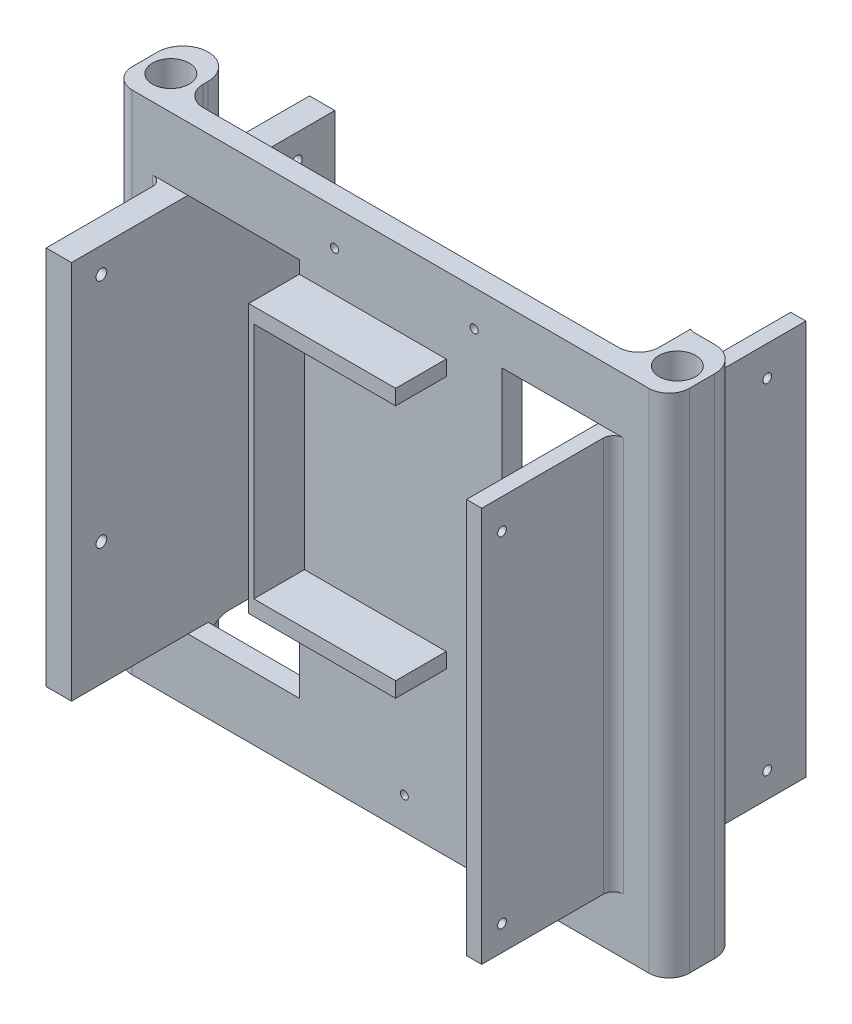
SolidWorks part; units mm, degrees
ref_plane "Front Plane" through (0, 0, 0) normal (0, 0, 1) x (1, 0, 0)
ref_plane "Top Plane" through (0, 0, 0) normal (0, 1, 0) x (1, 0, 0)
ref_plane "Right Plane" through (0, 0, 0) normal (1, 0, 0) x (0, 0, -1)
sketch "Sketch2" plane through (0, 0, 0) normal (0, 1, 0) x (1, 0, 0)
  line L0 (0, 11.43) -> (0, 5.08)
  line L1 (5.08, 0) -> (134.62, 0)
  line L2 (139.7, 5.08) -> (139.7, 11.43)
  line L3 (12.7, 11.43) -> (12.7, 5.08)
  line L4 (12.7, 5.08) -> (127, 5.08)
  line L5 (127, 5.08) -> (127, 11.43)
  line L6 (6.35, 0) -> (6.35, 3.81) construction
  line L7 (127, 11.43) -> (127, 17.78)
  line L8 (127, 17.78) -> (133.35, 17.78)
  arc A2 (12.7, 11.43) -> (0, 11.43) centre (6.35, 11.43) ccw
  arc A3 (139.7, 11.43) -> (133.35, 17.78) centre (133.35, 11.43) ccw
  circle A4 centre (6.35, 8.4138) radius 4.6037
  circle A5 centre (133.35, 8.4138) radius 4.6037
  arc A6 (134.62, 0) -> (139.7, 5.08) centre (134.62, 5.08) ccw
  arc A7 (0, 5.08) -> (5.08, 0) centre (5.08, 5.08) ccw
  point P12 (38.0611, -3.1951)
  point P23 (0, 0)
  dimension "D1" = 9.2075
  dimension "D5" = 5.08
  dimension "D2" = 127
  dimension "D3" = 139.7
  dimension "D4" = 5.08
  dimension "D6" = 3.81
extrude "Boss-Extrude1" add sketch "Sketch2" along normal blind 127 contours L5 L7 L8 A3 L2 A6 L1 A7 L0 A2 L3 L4
sketch "Sketch3" plane through (0, 127, 0) normal (0, 1, 0) x (1, 0, 0)
  circle A0 centre (133.35, 8.4138) radius 4.6037 construction
  circle A1 centre (6.35, 8.4138) radius 4.6037 construction
  circle A2 centre (133.35, 8.4138) radius 4.6037
  circle A3 centre (6.35, 8.4138) radius 4.6037
extrude "Cut-Extrude1" cut sketch "Sketch3" against normal up to surface (127 mm away) up to face at (75.7423, 0, -8.7028)
sketch "Sketch4" plane through (0, 0, 0) normal (0, 0, 1) x (1, 0, 0)
  line L0 (44.936, 120.65) -> (44.936, 11.4099) construction
  line L2 (-49.3824, 53.26) -> (90.3176, 53.26) construction
  line L8 (5.08, 127) -> (134.62, 127) construction
  line L9 (127, 127) -> (127, 0) construction
  line L10 (127, 127) -> (127, 0) construction
  line L11 (12.7, 127) -> (12.7, 0) construction
  line L12 (12.7, 127) -> (12.7, 0) construction
  circle A0 centre (69.32, 86.76) radius 1.35
  circle A1 centre (20.32, 86.76) radius 1.35
  circle A2 centre (20.32, 28.76) radius 1.35
  circle A3 centre (69.32, 28.76) radius 1.35
  circle A4 centre (62.436, 10.65) radius 1
  circle A5 centre (62.436, 95.65) radius 1
  circle A6 centre (44.936, 120.65) radius 1
  circle A7 centre (27.436, 95.65) radius 1
  circle A8 centre (27.436, 10.65) radius 1
  point P25 (83.5986, 53.26)
  point P30 (-32.3911, 53.26)
  dimension "D5" = 2.7
  dimension "D6" = 2
  dimension "D1" = 49
  dimension "D2" = 58
  dimension "D3" = 24.5
  dimension "D4" = 24.384
  dimension "D7" = 35
  dimension "D8" = 17.5
  dimension "D9" = 25
  dimension "D10" = 85
  dimension "D11" = 8.89
  dimension "D12" = 6.35
  dimension "D13" = 7.62
extrude "Cut-Extrude2" [suppressed] cut sketch "Sketch4" against normal up to surface (5.08 mm away)
sketch "Sketch12" plane through (0, 0, 0) normal (0, -1, 0) x (1, 0, 0)
  line L5 (127, -5.08) -> (68.58, -5.08)
  line L6 (127, -5.08) -> (127, -43.18)
  line L7 (127, -43.18) -> (68.58, -43.18)
  line L8 (68.58, -5.08) -> (68.58, -43.18)
  dimension "D1" = 58.42
  dimension "D2" = 38.1
extrude "Boss-Extrude4" [suppressed] add sketch "Sketch12" against normal blind 7.62 separate body
fillet "Fillet3" [suppressed] radius 6.35
sketch "Sketch13" [suppressed] plane through (0, 7.62, 0) normal (0, 1, 0) x (1, 0, 0)
  line L1 (127, 43.18) -> (38.1, 43.18)
  line L2 (127, 43.18) -> (127, 38.1)
  line L3 (127, 38.1) -> (38.1, 38.1)
  line L4 (38.1, 43.18) -> (38.1, 38.1)
  dimension "D1" = 5.08
  dimension "D2" = 88.9
extrude "Boss-Extrude5" [suppressed] add sketch "Sketch13" along normal up to surface (119.38 mm away)
sketch "Sketch14" [suppressed] plane through (0, 0, -43.18) normal (0, 0, -1) x (-1, 0, 0)
  line L0 (-109.68, 120.65) -> (-43.18, 120.65) construction
  line L1 (-76.43, 120.65) -> (-76.43, 71.1303) construction
  line L2 (-127, 127) -> (-38.1, 127) construction
  line L3 (-38.1, 127) -> (-38.1, 7.62) construction
  circle A0 centre (-109.68, 120.65) radius 1.1
  circle A1 centre (-109.68, 36.65) radius 1.1
  circle A2 centre (-43.18, 120.65) radius 1.1
  circle A3 centre (-43.18, 36.65) radius 1.1
  dimension "D1" = 2.2
  dimension "D2" = 66.5
  dimension "D3" = 84
  dimension "D4" = 6.35
  dimension "D5" = 5.08
extrude "Cut-Extrude5" [suppressed] cut sketch "Sketch14" against normal up to surface (5.08 mm away)
sketch "Sketch15" [suppressed] plane through (0, 0, 0) normal (0, 0, 1) x (1, 0, 0)
  line L0 (127, 7.62) -> (68.58, 7.62) construction
  line L1 (127, 7.62) -> (68.58, 7.62)
  line L2 (68.58, 7.62) -> (68.58, 24.13)
  line L3 (68.58, 24.13) -> (127, 24.13)
  line L4 (127, 24.13) -> (127, 7.62)
  dimension "D1" = 16.51
extrude "Cut-Extrude6" [suppressed] cut sketch "Sketch15" against normal up to surface (5.08 mm away)
fillet "Fillet4" [suppressed] radius 6.35
sketch "Sketch17" [suppressed] plane through (0, 0, -43.18) normal (0, 0, -1) x (-1, 0, 0)
  line L1 (-68.58, 7.62) -> (-38.1, 7.62)
  line L4 (-38.1, 7.62) -> (-38.1, 26.67)
  line L5 (-38.1, 127) -> (-38.1, 7.62) construction
  spline S0 degree 2 poles (-68.58, 7.62) (-57.8979, 23.0749) (-38.1, 26.67) knots 0 0 0 1 1 1
  dimension "D1" = 19.05
extrude "Cut-Extrude8" [suppressed] cut sketch "Sketch17" against normal up to surface (5.08 mm away) contours L1 L4 S0
sketch "Sketch18" plane through (0, 0, 0) normal (0, 0, 1) x (1, 0, 0)
  line L0 (5.08, 127) -> (134.62, 127) construction
  line L1 (119.38, 114.3) -> (88.9, 114.3)
  line L2 (119.38, 114.3) -> (119.38, 99.06)
  line L3 (119.38, 99.06) -> (88.9, 99.06)
  line L4 (88.9, 114.3) -> (88.9, 99.06)
  line L5 (134.62, 127) -> (134.62, 0) construction
  dimension "D1" = 30.48
  dimension "D2" = 15.24
  dimension "D3" = 12.7
  dimension "D4" = 15.24
extrude "Cut-Extrude9" [suppressed] cut sketch "Sketch18" against normal up to surface (5.08 mm away)
sketch "Sketch19" plane through (0, 0, -5.08) normal (0, 0, -1) x (-1, 0, 0)
  line L1 (-97.79, 113.03) -> (-125.73, 113.03)
  line L2 (-97.79, 113.03) -> (-97.79, 13.97)
  line L3 (-97.79, 13.97) -> (-125.73, 13.97)
  line L4 (-125.73, 113.03) -> (-125.73, 13.97)
  line L5 (0, 127) -> (0, 0) construction
  line L6 (-127, 127) -> (-127, 0) construction
  point P10 (0, 63.5)
  point P11 (-97.79, 63.5)
  dimension "D1" = 99.06
  dimension "D2" = 27.94
  dimension "D3" = 1.27
extrude "Cut-Extrude10" cut sketch "Sketch19" against normal through all both and the other way through all
sketch "Sketch20" plane through (125.73, 0, 0) normal (1, 0, 0) x (0, 0, -1)
  line L0 (5.08, 113.03) -> (48.26, 113.03)
  line L1 (48.26, 113.03) -> (48.26, 13.97)
  line L2 (48.26, 13.97) -> (5.08, 13.97)
  line L4 (0, 113.03) -> (-33.02, 113.03)
  line L5 (-33.02, 113.03) -> (-33.02, 13.97)
  line L6 (-33.02, 13.97) -> (0, 13.97)
  line L7 (0, 13.97) -> (5.08, 13.97)
  line L8 (0, 113.03) -> (5.08, 113.03)
  dimension "D1" = 43.18
  dimension "D2" = 33.02
sketch "Sketch21" plane through (0, 0, 0) normal (0, -1, 0) x (1, 0, 0)
  line L0 (6.35, -8.4138) -> (133.35, -8.4138) construction
  circle A0 centre (69.85, -8.4138) radius 69.85
extrude "Boss-Extrude6" add sketch "Sketch20" against normal blind 3.81
sketch "Sketch23" plane through (121.92, 0, 0) normal (-1, 0, 0) x (0, 0, 1)
  line L0 (33.02, 113.03) -> (33.02, 13.97) construction
  line L1 (33.02, 13.97) -> (0, 13.97) construction
  circle A0 centre (27.94, 105.4583) radius 1.1
  circle A1 centre (27.94, 20.32) radius 1.1
  circle A2 centre (-38.56, 20.32) radius 1.1
  circle A3 centre (-38.56, 105.4583) radius 1.1
  dimension "D1" = 2.2
  dimension "D2" = 2.2
  dimension "D3" = 2.2
  dimension "D4" = 2.2
  dimension "D5" = 85.1383
  dimension "D6" = 66.5
  dimension "D7" = 5.08
  dimension "D8" = 6.35
extrude "Cut-Extrude11" cut sketch "Sketch23" against normal through all both
sketch "Sketch26" plane through (0, 0, -5.08) normal (0, 0, -1) x (-1, 0, 0)
  line L1 (-19.05, 111.125) -> (-12.7, 111.125)
  line L2 (-19.05, 111.125) -> (-19.05, 15.875)
  line L3 (-19.05, 15.875) -> (-12.7, 15.875)
  line L4 (-12.7, 111.125) -> (-12.7, 15.875)
  line L5 (-12.7, 127) -> (-12.7, 0) construction
  line L6 (-35.9191, 127) -> (-35.9191, 0) construction
  line L7 (-12.7, 127) -> (-127, 127) construction
  line L8 (-139.7, 0) -> (0, 0) construction
  point P12 (-35.9191, 63.5)
  point P13 (-19.05, 63.5)
  dimension "D1" = 95.25
  dimension "D2" = 6.35
  dimension "D3" = 0
extrude "Boss-Extrude8" add sketch "Sketch26" along normal blind 31.75 and the other way blind 34.29
sketch "Sketch27" plane through (0, 0, -5.08) normal (0, 0, -1) x (-1, 0, 0)
  line L0 (-19.05, 111.125) -> (-19.05, 15.875) construction
  line L1 (-19.05, 15.875) -> (-46.99, 15.875)
  line L2 (-19.05, 15.875) -> (-19.05, 111.125)
  line L3 (-19.05, 111.125) -> (-46.99, 111.125)
  line L4 (-46.99, 15.875) -> (-46.99, 111.125)
  line L5 (-12.7, 127) -> (-127, 127) construction
  dimension "D1" = 95.25
  dimension "D2" = 27.94
  dimension "D3" = 15.875
extrude "Cut-Extrude12" cut sketch "Sketch27" against normal through all both and the other way through all
sketch "Sketch32" plane through (0, 0, -5.08) normal (0, 0, -1) x (-1, 0, 0)
  line L0 (-73.305, 111.8207) -> (-73.305, 75.52) construction
  line L1 (-73.305, 75.52) -> (-84.3936, 75.52) construction
  line L2 (-139.7, 0) -> (0, 0) construction
  line L3 (-97.79, 13.97) -> (-97.79, 113.03) construction
  circle A0 centre (-90.805, 118.02) radius 1
  circle A1 centre (-55.805, 118.02) radius 1
  circle A2 centre (-55.805, 33.02) radius 1
  circle A3 centre (-90.805, 33.02) radius 1
  circle A4 centre (-73.305, 8.02) radius 1
  dimension "D1" = 2
  dimension "D4" = 2
  dimension "D2" = 35
  dimension "D3" = 85
  dimension "D5" = 25
  dimension "D6" = 33.02
  dimension "D7" = 6.985
sketch "Sketch34" plane through (12.7, 0, 0) normal (-1, 0, 0) x (0, 0, 1)
  line L0 (-2.805, 91.5345) -> (-2.805, 75.775) construction
  line L1 (-2.805, 75.775) -> (-47.3151, 75.775) construction
  line L4 (-11.43, 111.125) -> (-36.83, 111.125) construction
  line L5 (-36.83, 15.875) -> (-36.83, 111.125) construction
  circle A0 centre (-27.305, 104.775) radius 1.35
  circle A1 centre (21.695, 104.775) radius 1.35
  circle A2 centre (21.695, 46.775) radius 1.35
  circle A3 centre (-27.305, 46.775) radius 1.35
  dimension "D1" = 2.7
  dimension "D2" = 49
  dimension "D3" = 58
  dimension "D4" = 6.35
  dimension "D5" = 9.525
extrude "Cut-Extrude13" cut sketch "Sketch32" against normal through all both and the other way through all
extrude "Cut-Extrude15" cut sketch "Sketch34" against normal blind 15.24
sketch "Sketch35" plane through (0, 0, 0) normal (0, 0, 1) x (1, 0, 0)
  line L0 (48.26, 104.1415) -> (48.26, 44.4515)
  line L1 (48.26, 44.4515) -> (83.82, 44.4515)
  line L2 (83.82, 44.4515) -> (83.82, 40.6415)
  line L3 (83.82, 40.6415) -> (46.99, 40.6415)
  line L5 (19.05, 111.125) -> (46.99, 111.125) construction
  line L7 (83.82, 107.9515) -> (83.82, 104.1415)
  line L8 (83.82, 104.1415) -> (48.26, 104.1415)
  line L9 (46.99, 40.6415) -> (46.99, 107.9515)
  line L10 (46.99, 107.9515) -> (83.82, 107.9515)
  line L11 (46.99, 111.125) -> (46.99, 15.875) construction
  dimension "D1" = 59.69
  dimension "D2" = 35.56
  dimension "D3" = 3.81
  dimension "D4" = 36.83
  dimension "D5" = 3.1735
  dimension "D6" = 35.56
  dimension "D7" = 3.81
  dimension "D8" = 0
extrude "Boss-Extrude10" add sketch "Sketch35" along normal blind 12.7
sketch "Sketch36" plane through (0, 13.97, 0) normal (0, -1, 0) x (1, 0, 0)
  line L1 (127, -17.78) -> (125.73, -17.78)
  line L2 (127, -17.78) -> (127, -5.08)
  line L3 (127, -5.08) -> (125.73, -5.08)
  line L4 (125.73, -17.78) -> (125.73, -5.08)
extrude "Boss-Extrude11" add sketch "Sketch36" against normal up to surface (99.06 mm away) up to face at (123.825, 113.03, -26.67)
fillet "Fillet5" radius 2.54 1 edges at (12.7, 63.5, -11.43) type face fillet first side face at (12.7, 48.125, -27.305) second side face at (8.4667, 63.5, -13.5467)
fillet "Fillet6" radius 2.54 3 edges at (125.73, 63.5, 0) (12.7, 63.5, 0) (125.73, 63.5, -17.78)
fillet "Fillet7" radius 5.08 8 edges at (124.46, 113.03, -5.08) (127, 120.015, -5.08) (127, 6.985, -5.08) (124.46, 13.97, -5.08) (15.875, 15.875, -5.08) (15.875, 111.125, -5.08) (12.7, 119.0625, -5.08) (12.7, 7.9375, -5.08)
